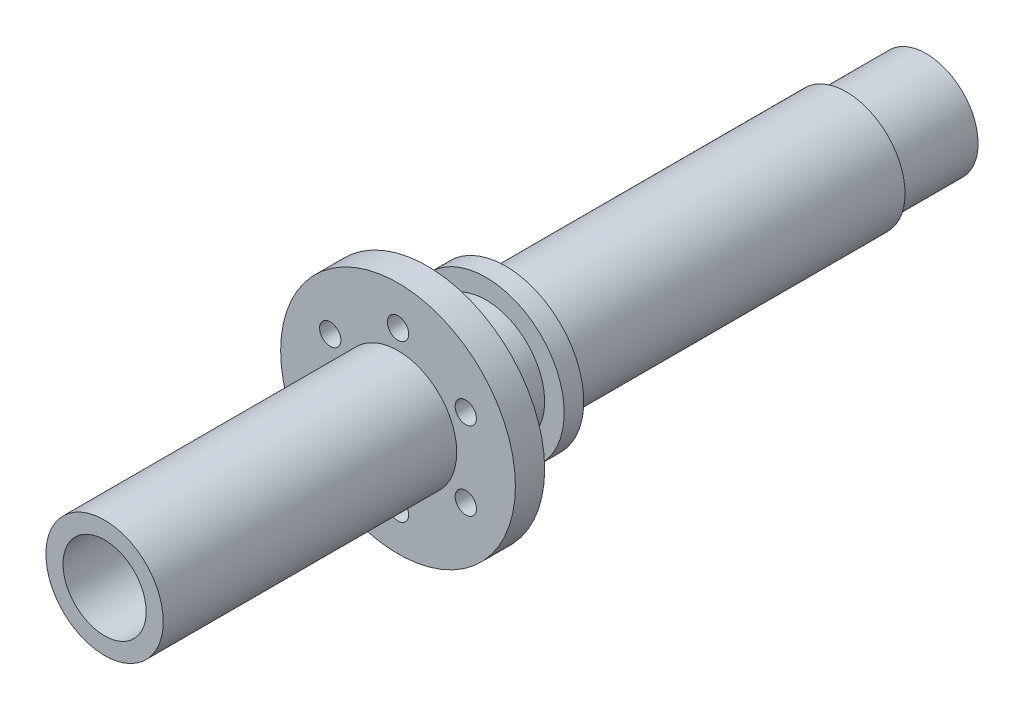
SolidWorks part; units mm, degrees
material "7075-T6 (SN)"
ref_plane "Front Plane" through (0, 0, 0) normal (0, 0, 1) x (1, 0, 0)
ref_plane "Top Plane" through (0, 0, 0) normal (0, 1, 0) x (1, 0, 0)
ref_plane "Right Plane" through (0, 0, 0) normal (1, 0, 0) x (0, 0, -1)
sketch "Sketch1" plane through (0, 0, 0) normal (0, 0, 1) x (1, 0, 0)
  circle A0 centre (0, 0) radius 9.525
  dimension "D1" = 19.05
extrude "Boss-Extrude1" add sketch "Sketch1" along normal blind 80.9625
cosmetic thread "Cosmetic Thread1" parameters "D1"=12.446, "D2"=16.3068
sketch "Sketch2" plane through (0, 0, 80.9625) normal (0, 0, 1) x (1, 0, 0)
  circle A0 centre (0, 0) radius 19.05
  dimension "D1" = 38.1
extrude "Boss-Extrude2" add sketch "Sketch2" along normal blind 4.7498
sketch "Sketch5" plane through (0, 0, 0) normal (0, 0, -1) x (-1, 0, 0)
  circle A0 centre (0, 0) radius 8.4328
  dimension "D1" = 16.8656
extrude "Cut-Extrude1" cut sketch "Sketch5" against normal blind 12.954 flip side to cut
ref_plane "Plane1" through (0, 0, 71.4375) normal (0, 0, -1) x (-1, 0, 0)
sketch "Sketch7" plane through (0, 0, 71.4375) normal (0, 0, -1) x (-1, 0, 0)
  circle A0 centre (0, 0) radius 12.7
  dimension "D1" = 25.4
extrude "Boss-Extrude3" add sketch "Sketch7" along normal blind 3.175
hole_wizard "#8-32 Tapped Hole1" positions "Sketch9" profile "Sketch8" tap size "#8-32" standard "Ansi Inch"
sketch "Sketch9" plane through (0, 0, 80.9625) normal (0, 0, -1) x (-1, 0, 0)
  point P0 (0, 12.7)
  point P18 (10.9985, 6.35)
  point P19 (10.9985, -6.35)
  point P20 (0, -12.7)
  point P21 (-10.9985, -6.35)
  point P22 (-10.9985, 6.35)
  dimension "D1" = 12.7
  dimension "D2" = 6
sketch "Sketch8" plane through (0, 12.7, 80.9625) normal (1, 0, 0) x (0, 1, 0)
  line L0 (0, 0) -> (0, 11.7058)
  line L1 (0, 11.7058) -> (1.7272, 10.668)
  line L2 (1.7272, 10.668) -> (1.7272, 0)
  line L5 (1.7272, 0) -> (0, 0)
  line L10 (0, 11.7058) -> (-1.7272, 10.668) construction
  line L11 (0, -6.35) -> (0, 107.95) construction
  dimension "Tap Drill Dia." = 3.4544
  dimension "Tap Drill Depth" = 10.668
  dimension "Drill Angle" = 118
sketch "Sketch6" plane through (0, 0, 0) normal (0, 0, -1) x (-1, 0, 0)
  circle A0 centre (0, 0) radius 6.35
  dimension "D1" = 12.7
extrude "Cut-Extrude2" cut sketch "Sketch6" against normal through all
sketch "Sketch10" plane through (0, 0, 85.7123) normal (0, 0, 1) x (1, 0, 0)
  circle A0 centre (0, 0) radius 9.525
  circle M5 centre (0, 0) radius 6.35
  dimension "D1" = 19.05
extrude "Boss-Extrude4" add sketch "Sketch10" along normal blind 47.625 contours A0 M5 region at (-9.2556, 0, 85.7123)
hole_wizard "5/8-11 Tapped Hole1" positions "Sketch12" profile "Sketch11" tap size "5/8-11" standard "Ansi Inch"
sketch "Sketch12" plane through (0, 0, 133.3373) normal (0, 0, 1) x (1, 0, 0)
  circle A0 centre (0, 0) radius 6.35 construction
  point P0 (0, 0)
sketch "Sketch11" plane through (0, 0, 133.3373) normal (1, 0, 0) x (0, -1, 0)
  line L0 (0, 0) -> (0, 29.4535)
  line L1 (0, 29.4535) -> (6.7462, 25.4)
  line L2 (6.7462, 25.4) -> (6.7462, 0)
  line L5 (6.7462, 0) -> (0, 0)
  line L10 (0, 29.4535) -> (-6.7462, 25.4) construction
  line L11 (0, -6.35) -> (0, 107.95) construction
  dimension "Tap Drill Dia." = 13.4925
  dimension "Tap Drill Depth" = 25.4
  dimension "Drill Angle" = 118
sketch "Sketch13" plane through (0, 0, 0) normal (0, 0, -1) x (-1, 0, 0)
  line L0 (0, -6.604) -> (0, 6.604) construction
  line L1 (-0.7937, -6.604) -> (-0.7938, 6.604)
  line L2 (0.7937, -6.604) -> (0.7937, 6.604)
  arc A0 (-0.7937, -6.604) -> (0.7937, -6.604) centre (0, -6.604) ccw
  arc A1 (0.7937, 6.604) -> (-0.7938, 6.604) centre (0, 6.604) ccw
  point P2 (0, 0)
  dimension "D1" = 1.5875
  dimension "D2" = 13.208
extrude "Cut-Extrude3" cut sketch "Sketch13" against normal blind 1.5875
fillet "Fillet1" radius 0.7937 4 edges at (0.7937, -6.3002, 0.7938) (-0.7937, -6.3002, 0.7938) (-0.7937, 6.3002, 0.7938) (0.7938, 6.3002, 0.7938)
chamfer "Chamfer1" distance 0.254 angle 45 8 edges at (6.35, 0, 0) (0.9874, -6.4087, 0) (0.9874, 6.4087, 0) (0, -7.3977, 0) (0, 7.3977, 0) (-0.9874, -6.4087, 0) (-0.9874, 6.4087, 0) (-6.35, 0, 0)
